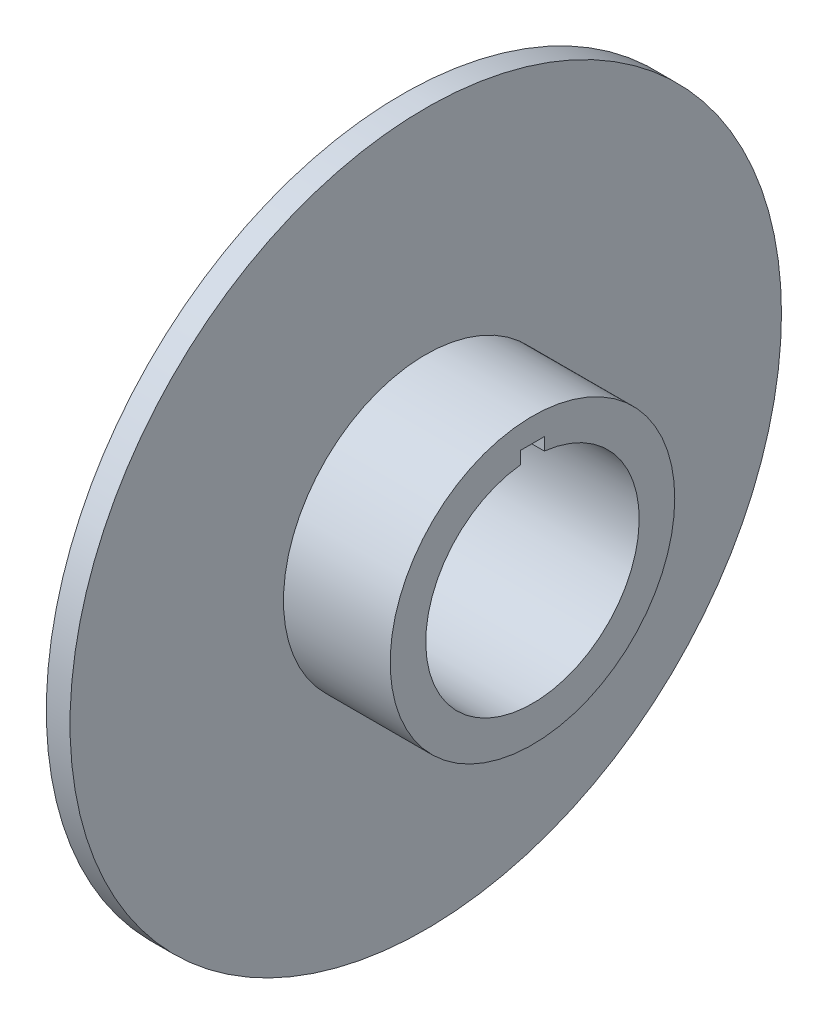
SolidWorks part; units mm, degrees
ref_plane "Front Plane" through (0, 0, 0) normal (0, 0, 1) x (1, 0, 0)
ref_plane "Top Plane" through (0, 0, 0) normal (0, 1, 0) x (1, 0, 0)
ref_plane "Right Plane" through (0, 0, 0) normal (1, 0, 0) x (0, 0, -1)
sketch "Sketch1" plane through (0, 0, 0) normal (1, 0, 0) x (0, 0, -1)
  line L1 (-5, 40) -> (5, 40)
  line L2 (-5, 40) -> (-5, 50)
  line L3 (-5, 50) -> (5, 50)
  line L4 (5, 40) -> (5, 50)
  line L5 (-5, 40) -> (5, 50) construction
  line L6 (-5, 50) -> (5, 40) construction
  circle A0 centre (0, 0) radius 45
  circle A1 centre (0, 0) radius 60
  circle A2 centre (0, 0) radius 150
  point P5 (0, 45)
  dimension "D1" = 90
  dimension "D3" = 120
  dimension "D4" = 300
  dimension "D2" = 10
extrude "Boss-Extrude1" add sketch "Sketch1" along normal mid plane 100 contours A1 A0 L2 L3 L4 region at (0, 0, 58.3029)
extrude "Boss-Extrude2" add sketch "Sketch1<3>" along normal mid plane 10 contours A2 A1 region at (0, 0, 145.7574)
sketch "Sketch1<3>" plane through (0, 0, 0) normal (1, 0, 0) x (0, 0, -1) same geometry as "Sketch1"
sketch "Sketch2" plane through (50, 0, 0) normal (1, 0, 0) x (0, 0, -1)
  line L1 (-5, 50) -> (5.0725, 50)
  line L2 (-5, 50) -> (-5, 44.7214)
  line L4 (5.0725, 50) -> (5.0725, 44.7132)
  arc A0 (5.0725, 44.7132) -> (-5, 44.7214) centre (0, 0) ccw
  arc A1 (-5, 44.7214) -> (5, 44.7214) centre (0, 0) ccw construction
